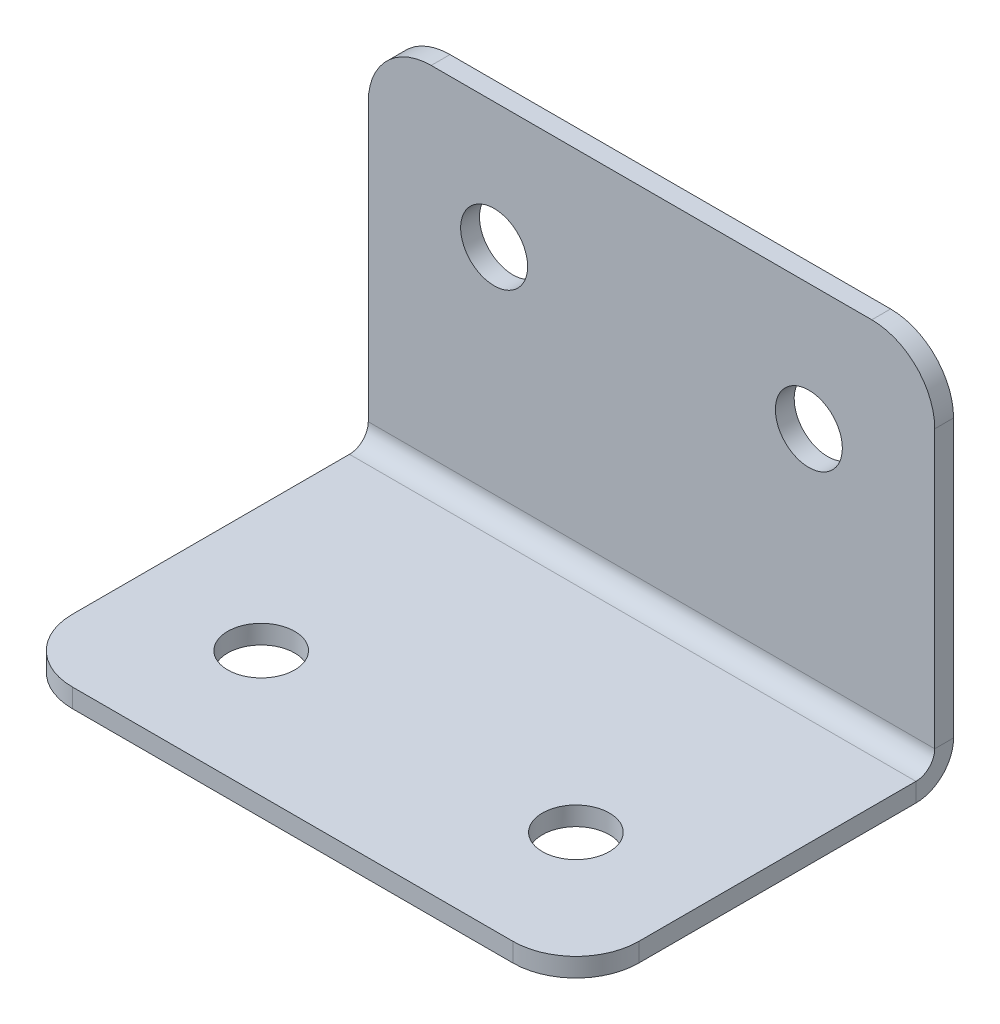
SolidWorks part; units mm, degrees
note: The reader was unsure of these and kept them because the rebuilt part matched: flange length of "Edge-Flange1".
material "Alloy Steel"
ref_plane "Front Plane" through (0, 0, 0) normal (0, 0, 1) x (1, 0, 0)
ref_plane "Top Plane" through (0, 0, 0) normal (0, 1, 0) x (1, 0, 0)
ref_plane "Right Plane" through (0, 0, 0) normal (1, 0, 0) x (0, 0, -1)
sketch "Sketch1" plane through (0, 0, 0) normal (0, 1, 0) x (1, 0, 0)
  line L1 (-28.575, -38.1) -> (28.575, -38.1)
  line L2 (-28.575, -38.1) -> (-28.575, 0)
  line L3 (-28.575, 0) -> (28.575, 0)
  line L4 (28.575, -38.1) -> (28.575, 0)
  line L5 (0, 0) -> (0, -38.1) construction
  line L6 (-28.575, -19.05) -> (28.575, -19.05) construction
  point P0 (0, -19.05)
  dimension "D1" = 38.1
  dimension "D2" = 57.15
base flange "Base-Flange1" sketch "Sketch1" thickness 1.8974 reverse thickness direction yes parameters "D1"=1.8974
edge flange "Edge-Flange1" sketch "Sketch8" flange angle 90 flange length 38.1 flange position material inside bend radius 1.8974 thickness 1.8974 relief rectangular parameters "D6"=10
sketch "Sketch8" plane through (0, 1.8974, 0) normal (0, 0, -1) x (-1, 0, 0)
  line L0 (-28.575, 0) -> (28.575, 0) construction
  line L1 (-28.575, 0) -> (28.575, 0)
  line L2 (-28.575, 0) -> (-28.575, 36.2026)
  line L3 (-28.575, 36.2026) -> (28.575, 36.2026)
  line L4 (28.575, 36.2026) -> (28.575, 0)
bend "EdgeBend1" bend radius 1.8974 bend angle 90 parameters "D5"=1
sketch "Sketch9" plane through (0, 1.8974, 0) normal (0, 1, 0) x (1, 0, 0)
  line L0 (-15.875, -25.4) -> (15.875, -25.4) construction
  line L1 (-28.575, -38.1) -> (28.575, -38.1) construction
  point P3 (0, -25.4)
  dimension "D1" = 31.75
  dimension "D2" = 12.7
hole_wizard "1/4 Clearance Hole1" positions "Sketch10" profile "Sketch11" hole size "1/4" standard "ANSI Inch" end condition up to next
sketch "Sketch10" plane through (0, 1.8974, 0) normal (0, 1, 0) x (1, 0, 0)
  point P0 (-15.875, -25.4)
  point P3 (15.875, -25.4)
sketch "Sketch11" plane through (-15.875, 1.8974, 25.4) normal (1, 0, 0) x (0, 0, 1)
  line L0 (0, 0) -> (0, 1.8974)
  line L1 (0, 1.8974) -> (3.3782, 1.8974)
  line L2 (3.3782, 1.8974) -> (3.3782, 0)
  line L5 (3.3782, 0) -> (0, 0)
  line L11 (0, -6.35) -> (0, 107.95) construction
  dimension "Thru Hole Dia." = 6.7564
  dimension "Thru Hole Depth" = 1.8974
sketch "Sketch12" plane through (0, 0, 1.8974) normal (0, 0, 1) x (1, 0, 0)
  line L0 (15.875, 25.4) -> (-15.875, 25.4) construction
  line L1 (-15.875, 1.8974) -> (15.875, 1.8974) construction
  line L2 (-28.575, 38.1) -> (28.575, 38.1) construction
  point P3 (0, 25.4)
  dimension "D1" = 12.7
hole_wizard "1/4 Clearance Hole2" positions "Sketch13" profile "Sketch14" hole size "1/4" standard "ANSI Inch" end condition up to next
sketch "Sketch13" plane through (0, 0, 1.8974) normal (0, 0, 1) x (1, 0, 0)
  point P0 (-15.875, 25.4)
  point P3 (15.875, 25.4)
sketch "Sketch14" plane through (-15.875, 25.4, 1.8974) normal (1, 0, 0) x (0, -1, 0)
  line L0 (0, 0) -> (0, 1.8974)
  line L1 (0, 1.8974) -> (3.3782, 1.8974)
  line L2 (3.3782, 1.8974) -> (3.3782, 0)
  line L5 (3.3782, 0) -> (0, 0)
  line L11 (0, -6.35) -> (0, 107.95) construction
  dimension "Thru Hole Dia." = 6.7564
  dimension "Thru Hole Depth" = 1.8974
fillet "Fillet1" radius 6.35 4 edges at (28.575, 0.9487, 38.1) (-28.575, 0.9487, 38.1) (-28.575, 38.1, 0.9487) (28.575, 38.1, 0.9487)
sketch "Bend-Lines1" [suppressed] plane through (0, 0, 0) normal (0, 1, 0) x (1, 0, 0)
sketch "Bounding-Box1" [suppressed] plane through (0, 0, 0) normal (0, 1, 0) x (1, 0, 0)
sheet metal parameters "Sheet-Metal1" thickness 1.8974 parameters "D1"=1.9844
flat pattern "Flat-Pattern1" [suppressed]
sketch "Bend-Lines2" plane through (0, 0, 0) normal (0, 1, 0) x (1, 0, 0)
sketch3d "Bounding-Box2" [suppressed]
  line L0 (-28.575, 0, 0) -> (28.575, 0, 0) construction
  line L1 (-28.575, -38.1, 0) -> (28.575, -38.1, 0) construction
  line L2 (-28.575, 0, 0) -> (-28.575, -38.1, 0) construction
  line L3 (28.575, 0, 0) -> (28.575, -38.1, 0) construction
sheet metal parameters "Sheet-Metal2" thickness 1.8974 parameters "D1"=1.9844
flat pattern "Flat-Pattern1"
sketch "Bend-Lines2" plane through (0, 0, 0) normal (0, -1, 0) x (-1, 0, 0)
  line L0 (28.575, -1.5595) -> (-28.575, -1.5595) construction
  line L1 (28.575, -1.5595) -> (-28.575, -1.5595) construction
sketch3d "Bounding-Box2" [suppressed]
  line L0 (28.575, -38.1, 0) -> (28.575, 34.9811, 0) construction
  line L1 (-28.575, -38.1, 0) -> (-28.575, 34.9811, 0) construction
  line L2 (28.575, -38.1, 0) -> (-28.575, -38.1, 0) construction
  line L3 (28.575, 34.9811, 0) -> (-28.575, 34.9811, 0) construction
bend of the flat pattern "Flatten-<EdgeBend1>1"
sheet metal parameters "Sheet-Metal3" thickness 1.8974 parameters "D1"=1.9844
flat pattern "Flat-Pattern1"
sketch "Bend-Lines2" plane through (0, 0, 0) normal (0, -1, 0) x (-1, 0, 0)
  line L0 (28.575, -1.5595) -> (-28.575, -1.5595) construction
  line L1 (28.575, -1.5595) -> (-28.575, -1.5595) construction
sketch3d "Bounding-Box2" [suppressed]
  line L0 (28.575, -38.1, 0) -> (28.575, 34.9811, 0) construction
  line L1 (-28.575, -38.1, 0) -> (-28.575, 34.9811, 0) construction
  line L2 (28.575, -38.1, 0) -> (-28.575, -38.1, 0) construction
  line L3 (28.575, 34.9811, 0) -> (-28.575, 34.9811, 0) construction
bend of the flat pattern "Flatten-<EdgeBend1>1"
sheet metal parameters "Sheet-Metal4" thickness 1.8974 parameters "D1"=1.9844
flat pattern "Flat-Pattern1" [suppressed]
sketch "Bend-Lines2" plane through (0, 0, 0) normal (0, -1, 0) x (-1, 0, 0)
  line L0 (28.575, -1.5595) -> (-28.575, -1.5595) construction
  line L1 (28.575, -1.5595) -> (-28.575, -1.5595) construction
sketch3d "Bounding-Box2" [suppressed]
  line L0 (-28.575, -38.1, 0) -> (-28.575, 34.9811, 0) construction
  line L1 (28.575, -38.1, 0) -> (28.575, 34.9811, 0) construction
  line L2 (-28.575, -38.1, 0) -> (28.575, -38.1, 0) construction
  line L3 (-28.575, 34.9811, 0) -> (28.575, 34.9811, 0) construction
bend of the flat pattern "Flatten-<EdgeBend1>1"
sketch "Sketch12-1" plane through (0, 1.8974, 3.1189) normal (0, 1, 0) x (1, 0, 0)
  line L0 (15.875, 25.4) -> (-15.875, 25.4) construction
  line L2 (-22.225, 38.1) -> (22.225, 38.1)
  point P3 (0, 25.4)
  dimension "D1" = 12.7
